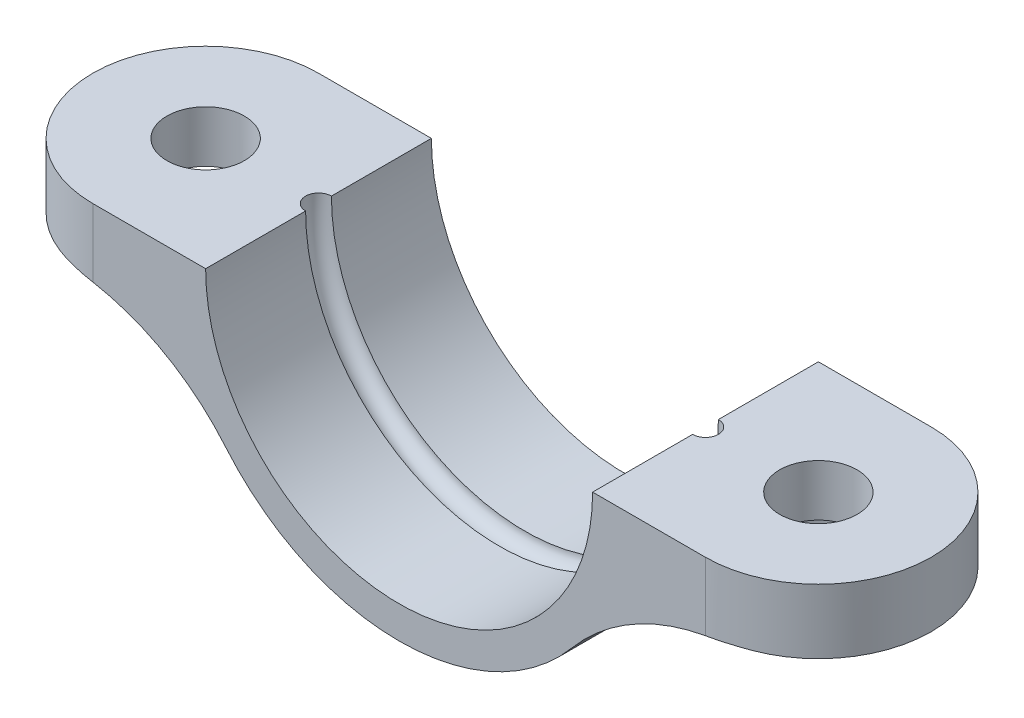
SolidWorks part; units mm, degrees
ref_plane "Plano frontal" through (0, 0, 0) normal (0, 0, 1) x (1, 0, 0)
ref_plane "Plano superior" through (0, 0, 0) normal (0, 1, 0) x (1, 0, 0)
ref_plane "Plano direito" through (0, 0, 0) normal (1, 0, 0) x (0, 0, -1)
sketch "Sketch2" plane through (0, 0, 0) normal (0, 0, 1) x (1, 0, 0)
  line L0 (30, 0) -> (65, 0)
  line L1 (65, 0) -> (65, -10)
  line L2 (65, -10) -> (53.619, -10)
  line L3 (0, 30) -> (0, 35) construction
  line L4 (-65, -10) -> (-53.619, -10)
  line L5 (-65, 0) -> (-65, -10)
  line L6 (-30, 0) -> (-65, 0)
  arc A0 (-30, 0) -> (30, 0) centre (0, 0) ccw
  arc A1 (-26.8095, -22.5) -> (26.8095, -22.5) centre (0, 0) ccw
  arc A2 (26.8095, -22.5) -> (53.619, -10) centre (53.619, -45) cw
  arc A3 (-26.8095, -22.5) -> (-53.619, -10) centre (-53.619, -45) ccw
  dimension "D1" = 60
  dimension "D2" = 70
  dimension "D5" = 35
  dimension "D3" = 35
  dimension "D4" = 10
extrude "Boss-Extrude1" add sketch "Sketch2" along normal mid plane 35
sketch "Sketch3" plane through (0, 0, 0) normal (0, 1, 0) x (1, 0, 0)
  line L1 (0, 0) -> (0, 38.9121) construction
  circle A0 centre (47.5, 0) radius 6
  circle A1 centre (-47.5, 0) radius 6
  dimension "D1" = 12
extrude "Cut-Extrude1" cut sketch "Sketch3" against normal blind 35
sketch "Sketch4" plane through (0, 0, 0) normal (0, 1, 0) x (1, 0, 0)
  line L0 (30, -17.5) -> (30, 17.5) construction
  line L1 (0, 0) -> (0, 35.1191) construction
  circle A0 centre (30, 0) radius 2
  dimension "D1" = 4
revolve "Cut-Revolve1" cut sketch "Sketch4" angle 360 about L1
sketch "Sketch5" plane through (0, 0, 0) normal (0, 1, 0) x (1, 0, 0)
  circle A0 centre (47.5, 0) radius 10
  circle A1 centre (-47.5, 0) radius 10
  dimension "D1" = 20
extrude "Cut-Extrude2" cut sketch "Sketch5" against normal blind 35 from offset 8 offset against normal yes
fillet "Fillet1" 2 edges at (-65, -5, 17.5) (-65, -5, -17.5) type full round first side face at (0, -12.1557, 17.5) second side face at (0, -12.1557, -17.5) middle face at (-65, -5, 0)
fillet "Fillet2" 2 edges at (65, -5, -17.5) (65, -5, 17.5) type full round first side face at (9.8096, -12.583, -17.5) second side face at (9.8096, -12.583, 17.5) middle face at (65, -5, 0)
